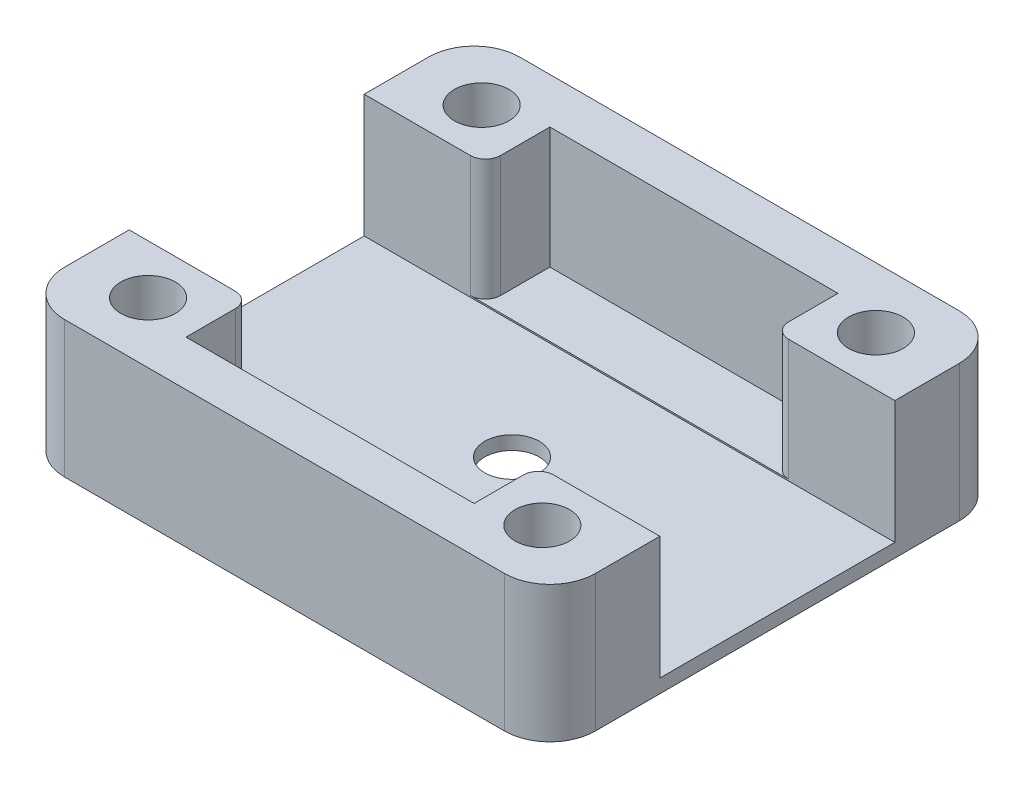
SolidWorks part; units mm, degrees
ref_plane "Front Plane" through (0, 0, 0) normal (0, 0, 1) x (1, 0, 0)
ref_plane "Top Plane" through (0, 0, 0) normal (0, 1, 0) x (1, 0, 0)
ref_plane "Right Plane" through (0, 0, 0) normal (1, 0, 0) x (0, 0, -1)
sketch "Sketch1" plane through (0, 0, 0) normal (0, 1, 0) x (1, 0, 0)
  line L1 (-17.5, -15) -> (17.5, -15)
  line L2 (-17.5, -15) -> (-17.5, 15)
  line L3 (-17.5, 15) -> (17.5, 15)
  line L4 (17.5, -15) -> (17.5, 15)
  line L5 (-17.5, -15) -> (17.5, 15) construction
  line L6 (-17.5, 15) -> (17.5, -15) construction
  point P0 (0, 0)
  dimension "D1" = 35
  dimension "D2" = 30
extrude "Boss-Extrude1" add sketch "Sketch1" along normal blind 9
sketch "Sketch3" plane through (0, 9, 0) normal (0, 1, 0) x (1, 0, 0)
  line L8 (14.5, -12) -> (14.5, 12)
  line L9 (14.5, 12) -> (-14.5, 12)
  line L10 (-14.5, 12) -> (-14.5, -12)
  line L11 (-14.5, -12) -> (14.5, -12)
  line L12 (14.5, -12) -> (14.5, 12)
  line L13 (14.5, 12) -> (-14.5, 12)
  line L14 (-14.5, 12) -> (-14.5, -12)
  line L15 (-14.5, -12) -> (14.5, -12)
  dimension "D1" = 3
extrude "Cut-Extrude1" cut sketch "Sketch3" against normal blind 8
sketch "Sketch4" plane through (-17.5, 0, 0) normal (-1, 0, 0) x (0, 0, 1)
  line L0 (-15, 0) -> (15, 0) construction
  line L1 (-7.75, 0.9) -> (7.75, 0.9)
  line L2 (-7.75, 0.9) -> (-7.75, 9)
  line L3 (-7.75, 9) -> (7.75, 9)
  line L4 (7.75, 0.9) -> (7.75, 9)
  line L5 (-7.75, 0.9) -> (7.75, 9) construction
  line L6 (-7.75, 9) -> (7.75, 0.9) construction
  line L7 (-15, 9) -> (15, 9) construction
  point P0 (0, 4.95)
  point P5 (0, 0)
  point P8 (0, 0)
  dimension "D1" = 8.1
  dimension "D2" = 15.5
extrude "Cut-Extrude2" cut sketch "Sketch4" against normal through all
sketch "Sketch5" plane through (0, 1, 0) normal (0, 1, 0) x (1, 0, 0)
  line L0 (14.5, 7.75) -> (-14.5, 7.75) construction
  line L1 (-14.5, 12) -> (-9.5, 12)
  line L2 (-14.5, 12) -> (-14.5, 7.75)
  line L3 (-14.5, 7.75) -> (-9.5, 7.75)
  line L4 (-9.5, 12) -> (-9.5, 7.75)
  line L5 (-14.5, -7.75) -> (14.5, -7.75) construction
  line L6 (14.5, 12) -> (9.5, 12)
  line L7 (14.5, 12) -> (14.5, 7.75)
  line L8 (14.5, 7.75) -> (9.5, 7.75)
  line L9 (9.5, 12) -> (9.5, 7.75)
  line L10 (14.5, -12) -> (9.5, -12)
  line L11 (14.5, -12) -> (14.5, -7.75)
  line L12 (14.5, -7.75) -> (9.5, -7.75)
  line L13 (9.5, -12) -> (9.5, -7.75)
  line L15 (-14.5, -12) -> (-9.5, -12)
  line L16 (-14.5, -12) -> (-14.5, -7.75)
  line L17 (-14.5, -7.75) -> (-9.5, -7.75)
  line L18 (-9.5, -12) -> (-9.5, -7.75)
  dimension "D1" = 5
extrude "Boss-Extrude2" add sketch "Sketch5" along normal up to surface (8 mm away) up to face at (0, 9, -10.625)
hole_wizard "M3 Clearance Hole1" positions "Sketch6" profile "Sketch7" hole size "M3" standard "ANSI Metric" end condition through all
sketch "Sketch6" plane through (0, 9, 0) normal (0, 1, 0) x (1, 0, 0)
  line L1 (-13, -11) -> (13, -11)
  line L2 (-13, -11) -> (-13, 11)
  line L3 (-13, 11) -> (13, 11)
  line L4 (13, -11) -> (13, 11)
  line L5 (-13, -11) -> (13, 11) construction
  line L6 (-13, 11) -> (13, -11) construction
  point P1 (0, 0)
  point P2 (13, 11)
  point P73 (-13, -11)
  point P74 (-13, 11)
  point P75 (13, -11)
  dimension "D1" = 26
  dimension "D2" = 22
sketch "Sketch7" plane through (0, 9, 0) normal (1, 0, 0) x (0, 0, 1)
  line L0 (0, 0) -> (0, 9)
  line L1 (0, 9) -> (1.8, 9)
  line L2 (1.8, 9) -> (1.8, 0)
  line L5 (1.8, 0) -> (0, 0)
  line L11 (0, -6.35) -> (0, 107.95) construction
  dimension "Thru Hole Dia." = 3.6
  dimension "Thru Hole Depth" = 9
fillet "Fillet1" radius 3 4 edges at (-17.5, 4.5, 15) (17.5, 4.5, 15) (17.5, 4.5, -15) (-17.5, 4.5, -15)
fillet "Fillet2" radius 1 4 edges at (9.5, 5, 7.75) (-9.5, 5, 7.75) (-9.5, 5, -7.75) (9.5, 5, -7.75)
